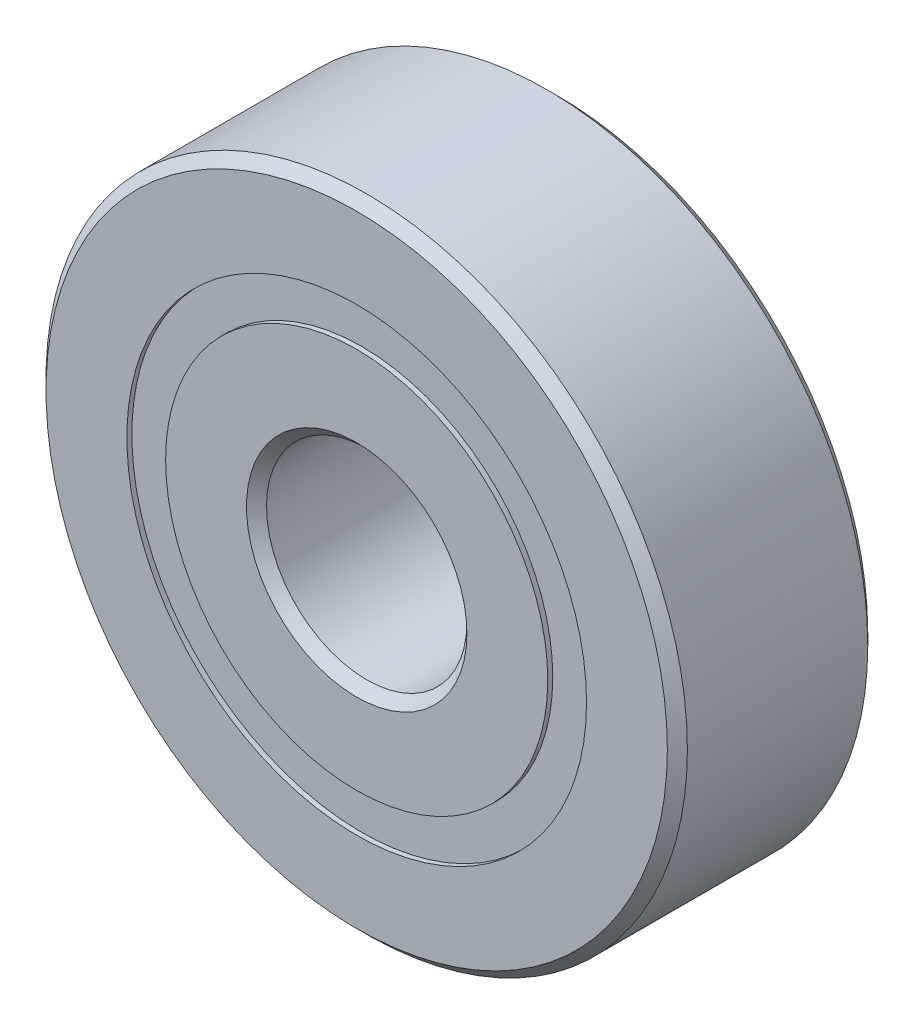
SolidWorks part; units mm, degrees
ref_plane "Front Plane" through (0, 0, 0) normal (0, 0, 1) x (1, 0, 0)
ref_plane "Top Plane" through (0, 0, 0) normal (0, 1, 0) x (1, 0, 0)
ref_plane "Right Plane" through (0, 0, 0) normal (1, 0, 0) x (0, 0, -1)
sketch "Sketch1" plane through (0, 0, 0) normal (1, 0, 0) x (0, 0, -1)
  line L0 (-2.5, 0) -> (2.5, 0) construction
  line L1 (0, 8) -> (0, -8) construction
  line L2 (2.25, 8) -> (-2.25, 8)
  line L3 (-2.25, 8) -> (-2.5, 7.75)
  line L4 (-2.5, 7.75) -> (-2.5, 5.7335)
  line L5 (-2.5, 5.7335) -> (-1.1111, 5.7335)
  line L6 (2.5, 5.7335) -> (1.1111, 5.7335)
  line L7 (2.5, 7.75) -> (2.5, 5.7335)
  line L8 (2.25, 8) -> (2.5, 7.75)
  line L9 (0, 8) -> (0, 5.25) construction
  line L10 (0, 5.25) -> (0, 2.5) construction
  arc A0 (-1.1111, 5.7335) -> (1.1111, 5.7335) centre (0, 5.25) cw
  point P14 (0, 2.5)
  dimension "Width" = 5
  dimension "OD" = 16
  dimension "D1" = 45
  dimension "D2" = 0.25
  dimension "Shaft Dia" = 5
  dimension "D3" = 2.2222
  dimension "D4" = 0.4835
revolve "Revolve1" add sketch "Sketch1" angle 360 about L0
sketch "Sketch3" plane through (0, 0, 0) normal (1, 0, 0) x (0, 0, -1)
  line L0 (-2.5, 4.7665) -> (-1.1111, 4.7665)
  line L1 (0, 8) -> (0, -8) construction
  line L2 (-2.5, 7.75) -> (-2.5, 5.7335) construction
  line L3 (-2.5, 4.7665) -> (-2.5, 2.75)
  line L4 (-2.25, 8) -> (-2.5, 7.75) construction
  line L5 (-2.5, 2.75) -> (-2.25, 2.5)
  line L6 (-2.25, 2.5) -> (2.25, 2.5)
  line L7 (2.25, 8) -> (2.25, -8) construction
  line L8 (2.25, 2.5) -> (2.5, 2.75)
  line L9 (2.5, -7.75) -> (2.5, 7.75) construction
  line L10 (2.5, 2.75) -> (2.5, 4.7665)
  line L11 (2.5, 4.7665) -> (1.1111, 4.7665)
  line L13 (2.25, 8) -> (2.5, 7.75) construction
  arc A0 (1.1111, 5.7335) -> (-1.1111, 5.7335) centre (0, 5.25) ccw construction
  arc A1 (1.1111, 4.7665) -> (-1.1111, 4.7665) centre (0, 5.25) cw
revolve "Revolve3" add sketch "Sketch3" angle 360 about L0
sketch "Sketch4" plane through (0, 0, 0) normal (1, 0, 0) x (0, 0, -1)
  line L0 (-1.2118, 5.25) -> (1.2118, 5.25)
  arc A2 (-1.2118, 5.25) -> (1.2118, 5.25) centre (0, 5.25) cw
  arc A3 (1.1111, 5.7335) -> (-1.1111, 5.7335) centre (0, 5.25) ccw construction
revolve "Revolve4" add sketch "Sketch4" angle 360 about L0
ref_axis "Axis1" through (0, 0, -2.5) along (0, 0, 1)
pattern_circular "CirPattern1" count 12 every 30 about axis through (0, 0, -2.5) along (0, 0, 1) of bodies 104
sketch "Sketch5" plane through (0, 0, 0) normal (1, 0, 0) x (0, 0, -1)
  line L0 (-2.5, 5.7335) -> (-1.1111, 5.7335) construction
  line L1 (-2.375, 5.7335) -> (-1.2118, 5.7335)
  line L2 (-2.375, 5.7335) -> (-2.375, 4.7665)
  line L3 (-2.375, 4.7665) -> (-1.2118, 4.7665)
  line L4 (-1.2118, 5.7335) -> (-1.2118, 4.7665)
  line L5 (-2.5, 4.7665) -> (-1.1111, 4.7665) construction
  line L6 (2.5, 5.7335) -> (1.1111, 5.7335) construction
  line L7 (2.375, 5.7335) -> (1.2118, 5.7335)
  line L8 (2.375, 5.7335) -> (2.375, 4.7665)
  line L9 (2.375, 4.7665) -> (1.2118, 4.7665)
  line L10 (1.2118, 5.7335) -> (1.2118, 4.7665)
  line L11 (2.5, 4.7665) -> (1.1111, 4.7665) construction
  line L12 (-2.25, 8) -> (-2.5, 7.75) construction
  point P18 (-2.375, 7.875)
revolve "Revolve5" add sketch "Sketch5" angle 360 about L0
sketch "Sketch6" plane through (0, 0, 0) normal (1, 0, 0) x (0, 0, -1)
  line L0 (2.5, 0) -> (-2.5, 0) construction
  line L1 (2.5, 5.7335) -> (1.4, 5.7335)
  line L2 (2.5, 5.7335) -> (2.5, 9.5)
  line L3 (2.5, 9.5) -> (1.4, 9.5)
  line L4 (1.4, 5.7335) -> (1.4, 9.5)
  dimension "Th" = 1.1
  dimension "Flange OD" = 19
revolve "Revolve6" [suppressed] add sketch "Sketch6" angle 360 about L0 other way angle 360
equation "\"D2@Sketch1\" = \"Width@Sketch1\"*.05"
equation "\"D3@Sketch1\" = \"Width@Sketch1\"/2.25"
equation "\"D4@Sketch1\" = (((\"OD@Sketch1\"-\"Width@Sketch1\")/2)/3.25)/3.5"
equation "\"D2@CirPattern1\" = 360/\"Balls@CirPattern1\""
